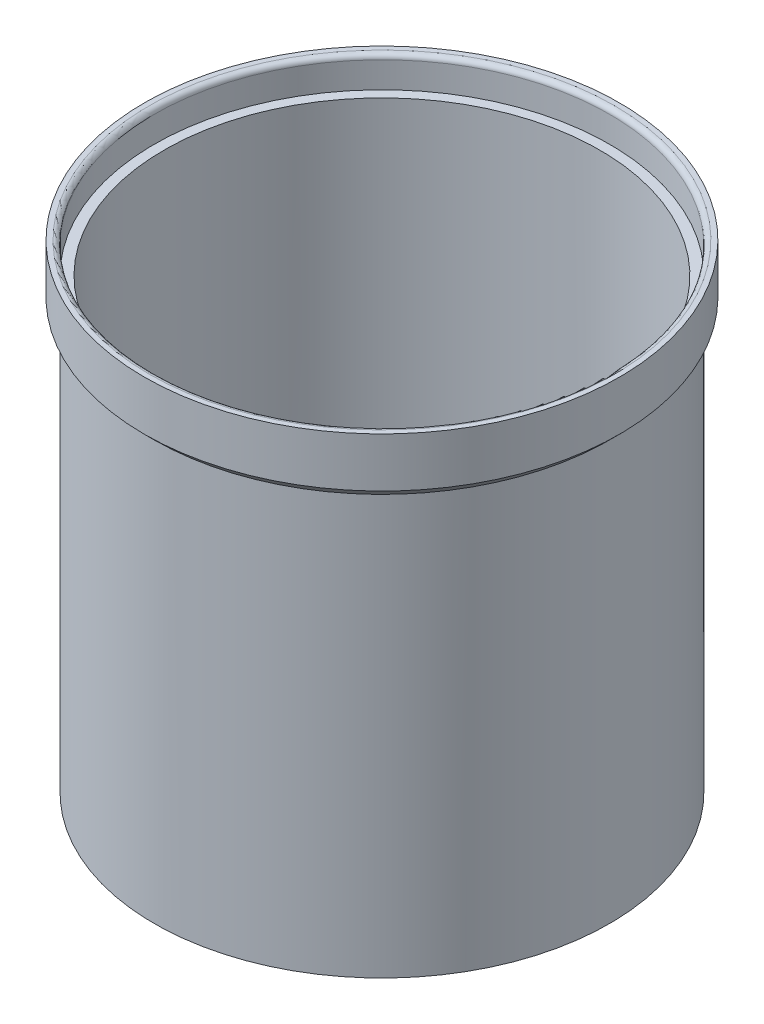
SolidWorks part; units mm, degrees
ref_plane "Front Plane" through (0, 0, 0) normal (0, 0, 1) x (1, 0, 0)
ref_plane "Top Plane" through (0, 0, 0) normal (0, 1, 0) x (1, 0, 0)
ref_plane "Right Plane" through (0, 0, 0) normal (1, 0, 0) x (0, 0, -1)
sketch "Sketch1" plane through (0, 0, 0) normal (0, 1, 0) x (1, 0, 0)
  circle A0 centre (0, 0) radius 36.8
  circle A1 centre (0, 0) radius 35.2
  dimension "D1" = 73.6
  dimension "D2" = 1.6
extrude "Boss-Extrude1" add sketch "Sketch1" along normal blind 70
sketch "Sketch2" plane through (0, 70, 0) normal (0, 1, 0) x (1, 0, 0)
  circle A1 centre (0, 0) radius 36.8
  circle A2 centre (0, 0) radius 36.8
  circle A3 centre (0, 0) radius 38.4
  dimension "D1" = 0
  dimension "D2" = 1.6
extrude "Boss-Extrude2" add sketch "Sketch2" along normal blind 5 and the other way blind 5
chamfer "Chamfer1" distance 2 angle 45 1 edges at (0, 65, 38.4)
fillet "Fillet1" radius 0.8 1 edges at (0, 75, 36.8)
sketch "Sketch3" plane through (0, 0, 0) normal (0, -1, 0) x (1, 0, 0)
  circle A0 centre (0, 0) radius 36.8 construction
  circle A1 centre (0, 0) radius 36.8
  circle A2 centre (0, 0) radius 36.2
  dimension "D1" = 0.6
extrude "Boss-Extrude3" add sketch "Sketch3" along normal blind 2.3
chamfer "Chamfer2" distance 1 angle 45 1 edges at (0, 0, 35.2)
fillet "Fillet2" radius 0.6 1 edges at (0, -2.3, -36.2)
